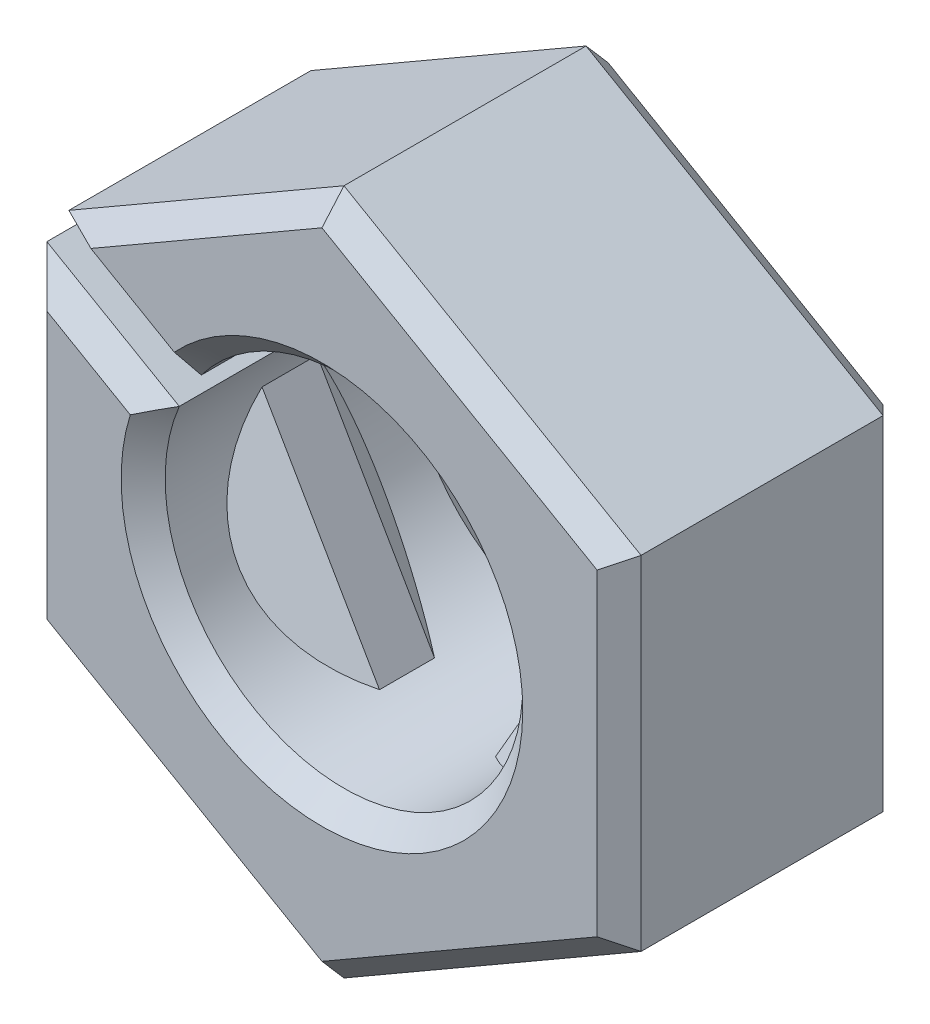
SolidWorks part; units mm, degrees
ref_plane "Front" through (0, 0, 0) normal (0, 0, 1) x (1, 0, 0)
ref_plane "Top" through (0, 0, 0) normal (0, 1, 0) x (1, 0, 0)
ref_plane "Right" through (0, 0, 0) normal (1, 0, 0) x (0, 0, -1)
sketch "Sketch1" plane through (0, 0, 0) normal (0, 0, 1) x (1, 0, 0)
  line L1 (2.7, -1.5588) -> (2.7, 1.5588)
  line L2 (2.7, 1.5588) -> (0, 3.1177)
  line L3 (0, 3.1177) -> (-2.7, 1.5588)
  line L4 (-2.7, 1.5588) -> (-2.7, -1.5588)
  line L5 (-2.7, -1.5588) -> (0, -3.1177)
  line L6 (0, -3.1177) -> (2.7, -1.5588)
  circle A0 centre (0, 0) radius 2.7 construction
  circle A1 centre (0, 0) radius 1.625
  dimension "D1" = 3.25
  dimension "D2" = 5.4
extrude "Boss-Extrude1" add sketch "Sketch1" along normal mid plane 2.6
sketch "Sketch3" plane through (0, 0, 0) normal (1, 0, 0) x (0, 0, -1)
  line L0 (-0.65, 1.625) -> (0.65, 1.625)
  line L1 (1.3, 1.625) -> (-1.3, 1.625) construction
  line L4 (0, 0) -> (0, 1.225) construction
  line L5 (0.65, 1.625) -> (0.25, 1.225)
  line L6 (0.25, 1.225) -> (-0.25, 1.225)
  line L7 (-0.25, 1.225) -> (-0.65, 1.625)
  dimension "D1" = 0.4
  dimension "D2" = 90
  dimension "D3" = 0.5
extrude "Clip" add sketch "Sketch3" along normal up to next and the other way up to next
pattern_circular "Clips x3" count 3 over 360 about axis through (0, 0, 1.3) along (0, 0, 1) of "Clip"
sketch "Sketch4" plane through (0, 0, 0) normal (0, 0, 1) x (1, 0, 0)
  line L0 (-2.7, 1.5588) -> (0, 0)
extrude "Split" cut sketch "Sketch4" against normal through all both and the other way through all thin thin type mid plane wall 0.4
chamfer "Deburs" distance 0.2 angle 45 18 edges at (1.4073, -0.8125, -1.3) (2.7, 0, -1.3) (1.35, 2.3383, -1.3) (-1.25, 2.396, -1.3) (-2.7, -0.1155, -1.3) (-1.35, -2.3383, -1.3) (1.35, -2.3383, -1.3) (1.4073, -0.8125, 1.3) (-1.35, -2.3383, 1.3) (-2.7, -0.1155, 1.3) (-1.25, 2.396, 1.3) (1.35, 2.3383, 1.3) (2.7, 0, 1.3) (1.35, -2.3383, 1.3) (-1.8983, 1.3269, -1.3) (-2.0983, 0.9805, -1.3) (-1.8983, 1.3269, 1.3) (-2.0983, 0.9805, 1.3)
equation "\"D1@Sketch1\"=\"Clearance Hole Diameter@Box Assy.Assembly\"+.1"
equation "\"D2@Sketch1\"=\"Nut Trap Diameter@Box Assy.Assembly\"-0.3mm"
equation "\"D1@Boss-Extrude1\"=\"Nut Trap Depth@Box Assy.Assembly\""
